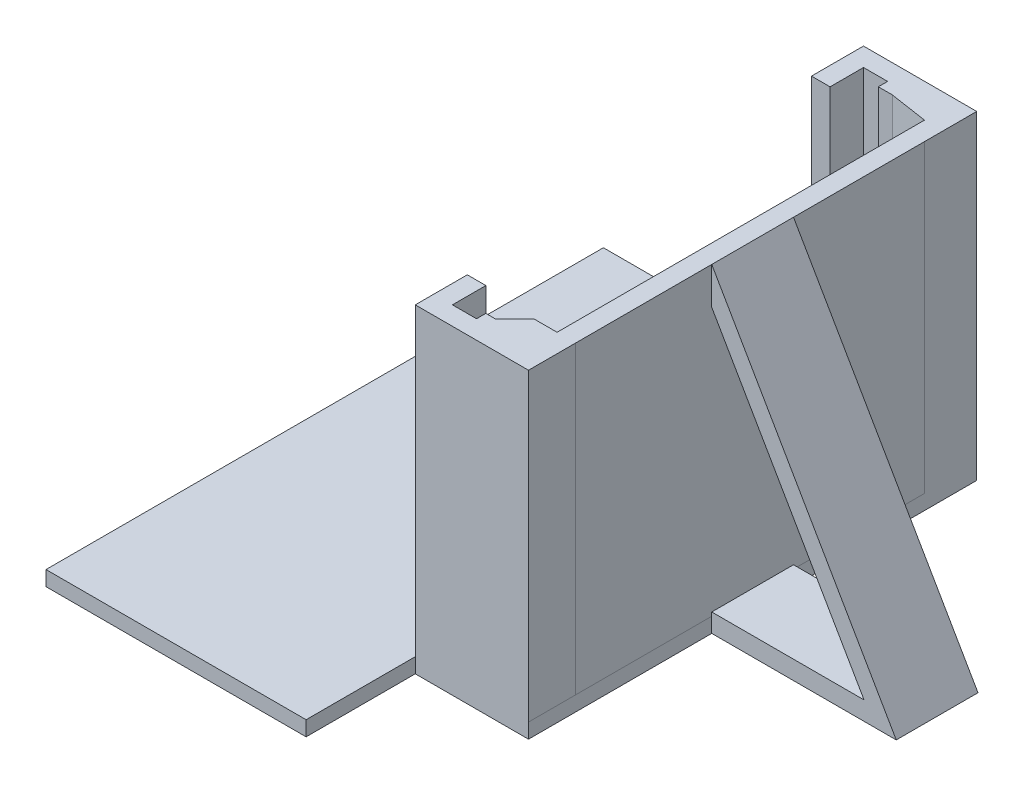
SolidWorks part; units mm, degrees
ref_plane "Front Plane" through (0, 0, 0) normal (0, 0, 1) x (1, 0, 0)
ref_plane "Top Plane" through (0, 0, 0) normal (0, 1, 0) x (1, 0, 0)
ref_plane "Right Plane" through (0, 0, 0) normal (1, 0, 0) x (0, 0, -1)
sketch "Sketch1" plane through (0, 0, 0) normal (0, 1, 0) x (1, 0, 0)
  line L1 (0, 0) -> (38.6999, 0)
  line L2 (0, 0) -> (0, 153.1937)
  line L3 (0, 153.1937) -> (38.6999, 153.1937)
  line L4 (38.6999, 0) -> (38.6999, 153.1937)
  line L5 (0, 153.1937) -> (-88.9, 153.1937)
  line L6 (0, 153.1937) -> (0, -37.3062)
  line L7 (0, -37.3062) -> (-88.9, -37.3063)
  line L8 (-88.9, 153.1937) -> (-88.9, -37.3063)
  dimension "D1" = 38.6999
  dimension "D2" = 153.1937
  dimension "D3" = 88.9
  dimension "D4" = 190.5
extrude "Boss-Extrude1" add sketch "Sketch1" along normal blind 5.08 contours L1 L4 L3 L2 | L5 L8 L7 L6 L2 region at (19.35, 0, -76.5969) region at (-44.45, 0, -57.9437)
sketch "Sketch3" plane through (0, 5.08, 0) normal (0, 1, 0) x (1, 0, 0)
  line L0 (6.65, 146.8438) -> (6.35, 146.8438)
  line L1 (6.65, 146.8438) -> (14.5875, 146.8438)
  line L2 (14.5875, 146.8438) -> (14.5875, 143.6687)
  line L3 (14.5875, 143.6687) -> (32.05, 143.6687)
  line L4 (6.35, 146.8438) -> (6.35, 135.4137)
  line L7 (32.05, 143.6687) -> (32.35, 143.6687)
  line L8 (32.35, 143.6687) -> (32.35, 135.4137)
  line L9 (32.35, 135.4137) -> (38.7, 135.4137)
  line L10 (38.7, 135.4137) -> (38.7, 153.1937)
  line L11 (38.7, 153.1937) -> (0, 153.1937)
  line L12 (6.35, 135.4137) -> (0, 135.4137)
  line L13 (0, 153.1937) -> (0, 135.4137)
  line L14 (-88.9, 153.1937) -> (38.6999, 153.1937) construction
  line L16 (14.5875, 9.525) -> (17.7625, 9.525)
  line L17 (10.6187, 146.8438) -> (10.6187, 76.5969) construction
  line L18 (10.6187, 76.5969) -> (61.4187, 76.5969) construction
  line L19 (38.6999, 0) -> (0, 0)
  line L20 (38.6999, 16.1157) -> (38.6999, 0)
  line L25 (14.5875, 6.35) -> (14.5875, 9.525)
  line L26 (6.65, 6.35) -> (14.5875, 6.35)
  line L27 (6.65, 6.35) -> (6.35, 6.35)
  line L28 (6.35, 6.35) -> (6.35, 17.78)
  line L29 (6.35, 17.78) -> (0, 17.78)
  line L30 (0, 0) -> (0, 17.78)
  line L31 (17.7625, 9.525) -> (24.3532, 16.1157)
  line L32 (24.3532, 16.1157) -> (38.6999, 16.1157)
  line L33 (19.35, 143.6687) -> (32.35, 141.6844)
  line L34 (38.6999, 0) -> (38.6999, 153.1937) construction
  point P14 (0, 0)
  point P19 (10.6187, 146.8438)
  dimension "D1" = 17.4625
  dimension "D2" = 7.9375
  dimension "D3" = 3.175
  dimension "D4" = 11.43
  dimension "D5" = 0.3
  dimension "D6" = 0.3
  dimension "D7" = 0
  dimension "D8" = 38.6999
  dimension "D9" = 6.35
  dimension "D10" = 6.35
  dimension "D11" = 6.35
  dimension "D12" = 6.35
  dimension "D13" = 70.2469
  dimension "D14" = 50.8
  dimension "D15" = 3.175
  dimension "D16" = 135
  dimension "D17" = 14.3467
  dimension "D18" = 90
  dimension "D19" = 18.08
  dimension "D20" = 90
  dimension "D21" = 4.7625
  dimension "D22" = 1.9844
extrude "Boss-Extrude2" add sketch "Sketch3" along normal blind 104.14 contours L13 L12 L4 L0 L1 L2 L3 L7 L8 L9 L10 | L30 L19 L20 L25 L26 L27 L28 L29 | L3 L33 L8 L7 region at (19.8693, 5.08, -146.5333) region at (28.0167, 5.08, -143.0073) region at (20.5173, 5.08, -7.298)
sketch "Sketch6" plane through (0, 0, -135.4137) normal (0, 0, 1) x (1, 0, 0)
  line L1 (32.35, 109.22) -> (38.7, 109.22)
  line L2 (32.35, 109.22) -> (32.35, 5.08)
  line L3 (32.35, 5.08) -> (38.7, 5.08)
  line L4 (38.7, 109.22) -> (38.7, 5.08)
  dimension "D1" = 104.14
  dimension "D2" = 6.35
extrude "Boss-Extrude3" add sketch "Sketch6" along normal up to surface (119.298 mm away) up to face at (31.5266, 57.15, -16.1157)
sketch "Sketch11" plane through (0, 0, -153.1937) normal (0, 0, -1) x (-1, 0, 0)
  line L0 (-38.6999, 109.22) -> (-101.7581, 0)
  line L1 (-38.6999, 109.22) -> (-38.6999, 0) construction
  line L4 (-38.6999, 96.52) -> (-94.4258, 0)
  line L5 (-94.4258, 0) -> (-101.7581, 0)
  line L6 (-38.6999, 96.52) -> (-38.6999, 109.22)
  line L8 (-38.6999, 109.22) -> (0, 109.22) construction
  line L9 (88.9, 0) -> (-38.6999, 0) construction
  dimension "D1" = 0
  dimension "D2" = 30
  dimension "D3" = 0
  dimension "D4" = 30
  dimension "D6" = 12.7
extrude "Boss-Extrude5" add sketch "Sketch11" along direction (0, 0, -1) on the side against the normal blind 27.94 from offset 62.6269 contours L6 L0 L5 L4 offset against normal yes
sketch "Sketch13" plane through (38.6999, 0, 0) normal (1, 0, 0) x (0, 0, -1)
  line L0 (0, 0) -> (153.1937, 0) construction
  line L1 (90.5669, 0) -> (62.6269, 0)
  line L2 (90.5669, 0) -> (90.5669, 6.35)
  line L3 (90.5669, 6.35) -> (62.6269, 6.35)
  line L4 (62.6269, 0) -> (62.6269, 6.35)
  line L5 (90.5669, 96.5199) -> (90.5669, 0) construction
  line L6 (62.6269, 109.2199) -> (62.6269, 0) construction
  dimension "D1" = 0
  dimension "D2" = 0
  dimension "D3" = 6.35
  dimension "D4" = 6.35
extrude "Boss-Extrude6" add sketch "Sketch13" along normal up to surface (63.0582 mm away) up to face at (70.2291, 54.61, -76.5969)
sketch "Sketch14" plane through (0, 0, -153.1937) normal (0, 0, -1) x (-1, 0, 0)
  line L0 (-14.5875, 5.08) -> (-6.35, 5.08) construction
  line L1 (-26, 36.83) -> (-14.5875, 36.83)
  line L2 (-26, 36.83) -> (-26, 55.88)
  line L3 (-26, 55.88) -> (-14.5875, 55.88)
  line L4 (-14.5875, 36.83) -> (-14.5875, 55.88)
  line L5 (88.9, 5.08) -> (0, 5.08) construction
  line L6 (-14.5875, 109.22) -> (-14.5875, 5.08) construction
  line L7 (-32.35, 109.22) -> (-32.35, 5.08) construction
  dimension "D1" = 31.75
  dimension "D2" = 50.8
  dimension "D3" = 0
  dimension "D4" = 6.35
extrude "Cut-Extrude1" cut sketch "Sketch14" against normal up to next
